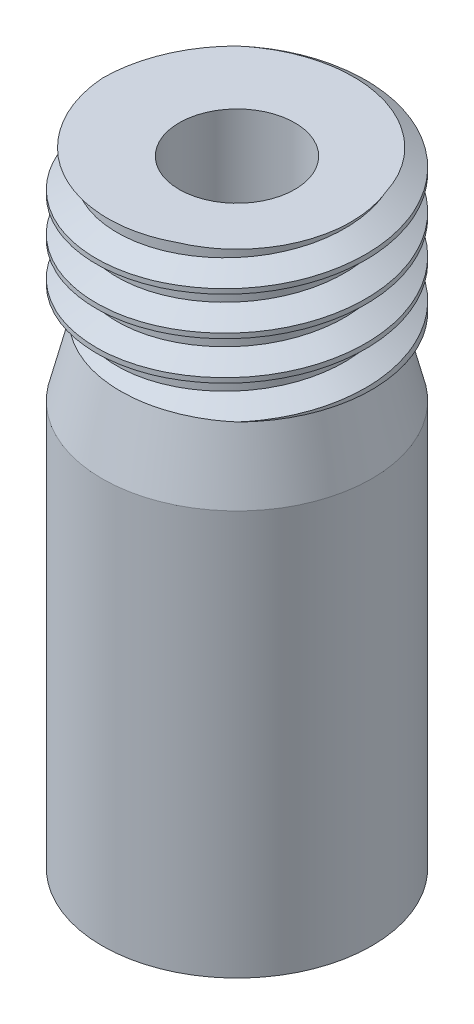
SolidWorks part; units mm, degrees
material "Alloy Steel"
ref_plane "Front Plane" through (0, 0, 0) normal (0, 0, 1) x (1, 0, 0)
ref_plane "Top Plane" through (0, 0, 0) normal (0, 1, 0) x (1, 0, 0)
ref_plane "Right Plane" through (0, 0, 0) normal (1, 0, 0) x (0, 0, -1)
sketch "MainBodyS" plane through (0, 0, 0) normal (0, 1, 0) x (1, 0, 0)
  circle A0 centre (0, 0) radius 3.5
  dimension "Dia" = 7
extrude "MAIN BODY" add sketch "MainBodyS" along normal blind 16
sketch "ContactEtchS" plane through (0, 0, 0) normal (0, -1, 0) x (1, 0, 0)
  circle A0 centre (0, 0) radius 2.5
  circle A1 centre (0, 0) radius 2
  circle A2 centre (0, 0) radius 3.5 construction
  dimension "OuterRefDia" = 5
  dimension "InnerRefDia" = 4
  dimension "Thickness" = 0.5
  dimension "DiaControl" = 1
extrude "CONTACT ETCH" cut sketch "ContactEtchS" against normal blind 0.01
sketch "ArmatureContactS" plane through (0, 0, 0) normal (0, -1, 0) x (-1, 0, 0)
  circle A0 centre (0, 0) radius 1
  circle A1 centre (0, 0) radius 0.75
  dimension "Dia" = 1.5
  dimension "RefOD" = 2
  dimension "Thickness" = 0.25
extrude "ARMATURE CONTACT" add sketch "ArmatureContactS" along normal blind 0.1
sketch "ArmatureThruHoleS" plane through (0, 0, 0) normal (0, -1, 0) x (1, 0, 0)
  circle A1 centre (0, 0) radius 0.75
  circle A2 centre (0, 0) radius 0.75
  dimension "D1" = 0
extrude "ARMATURE THRU HOLE" cut sketch "ArmatureThruHoleS" against normal through all
sketch "ThreadCutS" plane through (0, 0, 0) normal (0, 0, 1) x (1, 0, 0)
  line L1 (3.5, 16) -> (-3.5, 16) construction
  line L2 (3, 12.5) -> (3.5, 10.5)
  line L3 (3.5, 0) -> (3.5, 16) construction
  line L4 (3.5, 10.5) -> (3.5, 12.5)
  line L6 (0, 0) -> (0, 16) construction
  line L7 (3, 12.5) -> (3.5, 12.5)
  dimension "ChamferHeight" = 2
  dimension "YLoc" = 5.5
  dimension "ChamferWidth" = 0.5
revolve "THREAD CUT" cut sketch "ThreadCutS" angle 360 about L6
sketch "BoreS" plane through (0, 16, 0) normal (0, 1, 0) x (1, 0, 0)
  circle A0 centre (0, 0) radius 1.5
  dimension "Dia" = 3
extrude "BORE" cut sketch "BoreS" against normal offset from surface (13 mm away) 3 up to face at (0, 0, -2.5)
thread "M7 x .5" pitch 1 start angle 0, offset 1, length 0, pitch 1, diameter 7
ref_plane "Plane3" through (-3.5, 17, 0) normal (0, 0, 1) x (-1, 0, 0)
sketch "Thread Profile3" plane through (-3.5, 17, 0) normal (0, 0, 1) x (-1, 0, 0)
  line L0 (0, 0) -> (0, 1) construction
  line L11 (0, 0) -> (0, 0.875)
  line L12 (0, 0.875) -> (-0.5413, 0.5625)
  line L13 (-0.5413, 0.5625) -> (-0.5413, 0.3125)
  line L15 (-0.5413, 0.3125) -> (0, 0)
  line L17 (-0.5413, 0.4375) -> (0, 0.4375) construction
  point P2 (0, 0)
  dimension "Pitch" = 1
  dimension "Profile_Angle" = 60
  dimension "Profile_Land" = 0.25
  dimension "Profile_Height" = 0.5413
